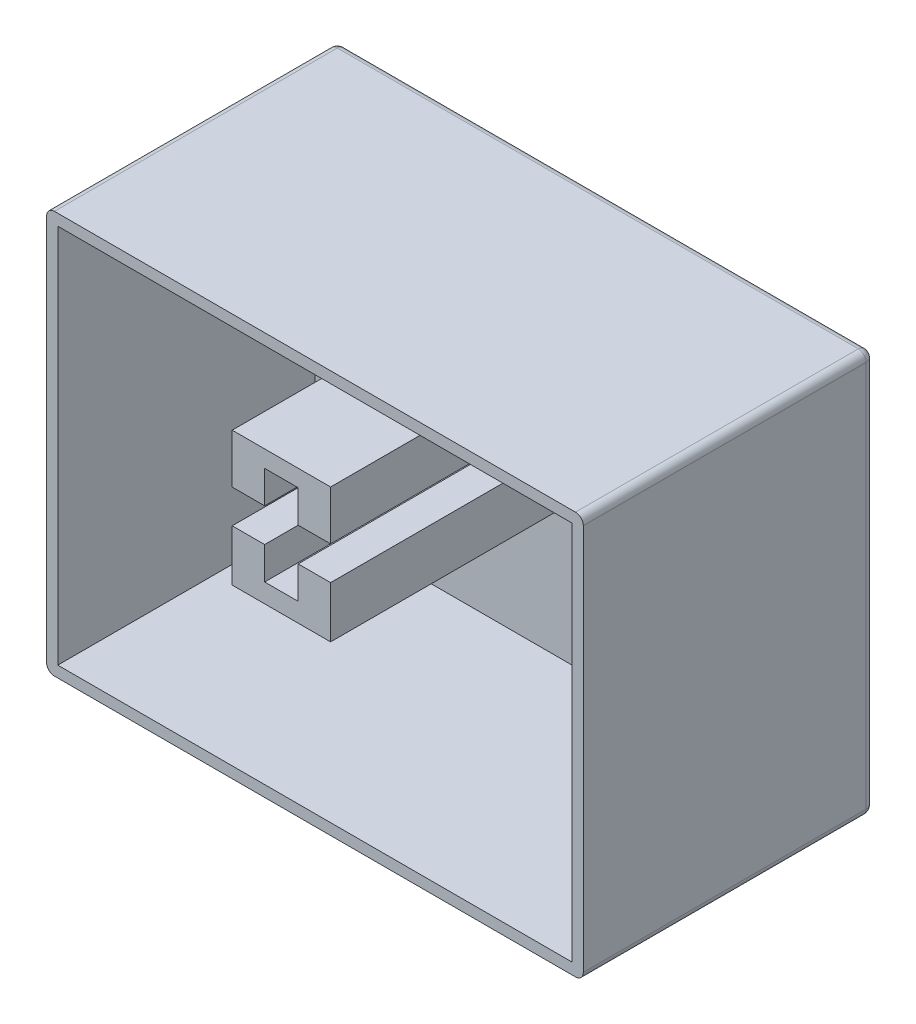
SolidWorks part; units mm, degrees
ref_plane "Front Plane" through (0, 0, 0) normal (0, 0, 1) x (1, 0, 0)
ref_plane "Top Plane" through (0, 0, 0) normal (0, 1, 0) x (1, 0, 0)
ref_plane "Right Plane" through (0, 0, 0) normal (1, 0, 0) x (0, 0, -1)
sketch "Sketch1" plane through (0, 0, 0) normal (0, 0, 1) x (1, 0, 0)
  line L1 (-12, -9) -> (12, -9)
  line L2 (-12, -9) -> (-12, 9)
  line L3 (-12, 9) -> (12, 9)
  line L4 (12, -9) -> (12, 9)
  line L5 (-12, -9) -> (12, 9) construction
  line L6 (-12, 9) -> (12, -9) construction
  point P0 (0, 0)
  dimension "D1" = 24
  dimension "D2" = 18
extrude "Boss-Extrude1" add sketch "Sketch1" along normal blind 13
fillet "Fillet1" radius 0.35 4 edges at (-12, 0, 0) (0, -9, 0) (12, 0, 0) (0, 9, 0)
fillet "Fillet2" radius 0.35 8 edges at (11.8975, 8.8975, 0.1025) (-11.8975, 8.8975, 0.1025) (11.8975, -8.8975, 0.1025) (-11.8975, -8.8975, 0.1025) (12, 9, 6.675) (-12, 9, 6.675) (12, -9, 6.675) (-12, -9, 6.675)
sketch "Sketch2" plane through (0, 0, 13) normal (0, 0, 1) x (1, 0, 0)
  line L0 (-11.65, -9) -> (11.65, -9) construction
  line L1 (11.5, 8.5) -> (-11.5, 8.5)
  line L2 (11.5, 8.5) -> (11.5, -8.5)
  line L3 (11.5, -8.5) -> (-11.5, -8.5)
  line L4 (-11.5, 8.5) -> (-11.5, -8.5)
  line L5 (12, -8.65) -> (12, 8.65) construction
  line L6 (11.65, 9) -> (-11.65, 9) construction
  line L7 (-12, 8.65) -> (-12, -8.65) construction
  dimension "D1" = 0.5
  dimension "D2" = 0.5
  dimension "D3" = 0.5
  dimension "D4" = 0.5
extrude "Cut-Extrude1" cut sketch "Sketch2" against normal blind 11.5
sketch "Sketch11" plane through (0, 0, 1.5) normal (0, 0, 1) x (1, 0, 0)
  line L1 (-5.2, -3) -> (-0.8, -3)
  line L2 (-5.2, -3) -> (-5.2, 3)
  line L3 (-5.2, 3) -> (-0.8, 3)
  line L4 (-0.8, -3) -> (-0.8, 3)
  line L5 (-5.2, -3) -> (-0.8, 3) construction
  line L6 (-5.2, 3) -> (-0.8, -3) construction
  line L7 (-11.5, 8.5) -> (-11.5, -8.5) construction
  point P0 (0, 0)
  dimension "D1" = 6
  dimension "D2" = 4.4
  dimension "D3" = 6.3
extrude "Boss-Extrude4" add sketch "Sketch11" along normal blind 10
sketch "Sketch12" plane through (0, 0, 11.5) normal (0, 0, 1) x (1, 0, 0)
  line L0 (-5.2, 3) -> (-5.2, -3) construction
  line L1 (-0.8, 0.7955) -> (-5.2, 0.7955)
  line L2 (-0.8, 0.7955) -> (-0.8, -0.7045)
  line L3 (-0.8, -0.7045) -> (-5.2, -0.7045)
  line L4 (-5.2, 0.7955) -> (-5.2, -0.7045)
  line L5 (-0.8, 0.7955) -> (-5.2, -0.7045) construction
  line L6 (-0.8, -0.7045) -> (-5.2, 0.7955) construction
  point P0 (-3, 0.0455)
  dimension "D1" = 1.5
extrude "Cut-Extrude6" cut sketch "Sketch12" against normal blind 10
sketch "Sketch13" plane through (0, 0, 11.5) normal (0, 0, 1) x (1, 0, 0)
  line L0 (-5.2, 0.7955) -> (-5.2, -0.7045) construction
  line L1 (-3.75, -2.1545) -> (-2.25, -2.1545)
  line L2 (-3.75, -2.1545) -> (-3.75, 2.2455)
  line L3 (-3.75, 2.2455) -> (-2.25, 2.2455)
  line L4 (-2.25, -2.1545) -> (-2.25, 2.2455)
  line L5 (-3.75, -2.1545) -> (-2.25, 2.2455) construction
  line L6 (-3.75, 2.2455) -> (-2.25, -2.1545) construction
  line L7 (-0.8, 0.7955) -> (-5.2, 0.7955) construction
  point P0 (-3, 0.0455)
extrude "Cut-Extrude7" cut sketch "Sketch13" against normal blind 10
